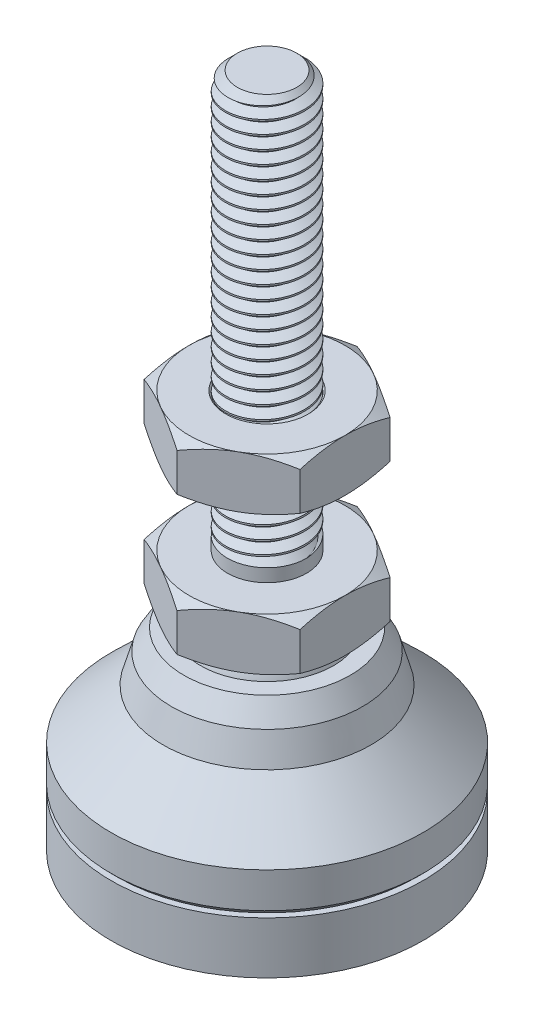
SolidWorks part; units mm, degrees
ref_plane "Front Plane" through (0, 0, 0) normal (0, 0, 1) x (1, 0, 0)
ref_plane "Top Plane" through (0, 0, 0) normal (0, 1, 0) x (1, 0, 0)
ref_plane "Right Plane" through (0, 0, 0) normal (1, 0, 0) x (0, 0, -1)
sketch "Sketch1" plane through (0, 0, 0) normal (0, 0, 1) x (1, 0, 0)
  line L0 (0, 0) -> (0, 41.275) construction
  line L1 (-9.525, 0) -> (9.525, 0) construction
  line L2 (-2.413, 41.275) -> (2.413, 41.275) construction
  line L3 (-4.7625, 12.7) -> (4.7625, 12.7) construction
  point P7 (0, 15.875)
  point P10 (0, 12.7)
  point P11 (-4.7625, 15.875)
  point P12 (0, 3.175)
  dimension "D1" = 3.175
sketch "Sketch2" plane through (0, 0, 0) normal (0, 0, 1) x (1, 0, 0)
  line L0 (0, 3.175) -> (0, 6.2865)
  line L1 (-4.2545, 12.7) -> (-4.7625, 12.7) construction
  line L2 (-5.842, 10.541) -> (-5.08, 11.811)
  line L3 (-5.08, 11.811) -> (-4.0605, 11.811)
  line L4 (-5.842, 10.541) -> (-6.35, 8.763)
  line L5 (-6.35, 8.763) -> (-9.525, 5.715)
  line L6 (-9.525, 5.715) -> (-9.525, 3.556)
  line L7 (-9.144, 3.175) -> (0, 3.175)
  line L8 (-5.842, 10.541) -> (0, 10.541) construction
  line L9 (-4.2545, 10.541) -> (-4.2545, 12.7) construction
  line L10 (-9.525, 3.556) -> (-9.144, 3.175)
  line L11 (-9.144, 3.175) -> (-9.525, 3.175) construction
  line L12 (-9.525, 3.175) -> (-9.525, 3.556) construction
  line L13 (0, 12.7) -> (0, 41.275) construction
  line L14 (-2.413, 41.275) -> (2.413, 41.275) construction
  line L15 (-4.7625, 12.7) -> (4.7625, 12.7) construction
  circle A0 centre (0, 10.541) radius 4.2545 construction
  arc A2 (-4.0605, 11.811) -> (0, 6.2865) centre (0, 10.541) ccw
  dimension "D1" = 12.7
  dimension "D2" = 11.684
  dimension "D3" = 10.16
  dimension "D4" = 0.508
  dimension "H3" = 1.778
  dimension "C1" = 0.381
  dimension "H4" = 1.27
  dimension "H2" = 3.048
  dimension "H1" = 2.54
revolve "Revolve1" add sketch "Sketch2" angle 360 about L0
sketch "Sketch12" plane through (0, 0, 0) normal (0, 0, 1) x (1, 0, 0)
  line L0 (0, 12.7) -> (-3.666, 12.7)
  line L1 (0, 12.7) -> (0, 6.2865)
  arc A0 (-3.666, 12.7) -> (0, 6.2865) centre (0, 10.541) ccw
  circle A1 centre (0, 10.541) radius 4.2545 construction
revolve "Revolve2" add sketch "Sketch12" angle 360 about L1
sketch "Sketch4" plane through (0, 12.7, 0) normal (0, 1, 0) x (1, 0, 0)
  line L1 (0, 5.4993) -> (-4.7625, 2.7496)
  line L2 (-4.7625, 2.7496) -> (-4.7625, -2.7496)
  line L3 (-4.7625, -2.7496) -> (0, -5.4993)
  line L4 (0, -5.4993) -> (4.7625, -2.7496)
  line L5 (4.7625, -2.7496) -> (4.7625, 2.7496)
  line L6 (4.7625, 2.7496) -> (0, 5.4993)
  circle A0 centre (0, 0) radius 4.7625 construction
extrude "Boss-Extrude1" add sketch "Sketch4" along normal up to vertex (3.175 mm away) up to point (0, 15.875, 0)
sketch "Sketch5" plane through (0, 0, 0) normal (1, 0, 0) x (0, 0, -1)
  line L0 (-6.236, 15.875) -> (-6.236, 12.7)
  line L1 (-6.236, 12.7) -> (-4.7625, 12.7)
  line L2 (-4.7625, 12.7) -> (-5.4993, 13.1254)
  line L3 (-5.4993, 13.1254) -> (-5.4993, 15.4496)
  line L4 (-5.4993, 15.4496) -> (-4.7625, 15.875)
  line L5 (-4.7625, 15.875) -> (-6.236, 15.875)
  line L9 (-5.4993, 15.875) -> (-5.4993, 12.7) construction
  dimension "D1" = 30
revolve "Cut-Revolve2" cut sketch "Sketch5" angle 360 about L0
sketch "Sketch6" plane through (0, 15.875, 0) normal (0, 1, 0) x (1, 0, 0)
  circle A0 centre (0, 0) radius 2.413
extrude "Boss-Extrude2" add sketch "Sketch6" along normal up to vertex (25.4 mm away) separate body up to point (0, 41.275, 0)
sketch "Sketch7" plane through (0, 41.275, 0) normal (0, 1, 0) x (1, 0, 0)
  circle A1 centre (0, 0) radius 2.413
  circle A2 centre (0, 0) radius 2.413
  point P0 (2.413, 0)
  dimension "D1" = 0
curve "Helix/Spiral1" pitch 0.7937 height 26.1937 turns 33 parameters "Pitch"=0.7937
sketch "Sketch8" plane through (0, 0, 0) normal (0, 0, 1) x (1, 0, 0)
  line L0 (2.4989, 42.0191) -> (2.4989, 41.2254) construction
  line L1 (2.4989, 41.2254) -> (1.8115, 41.6223) construction
  line L2 (1.8115, 41.6223) -> (2.4989, 42.0191) construction
  line L3 (1.8974, 41.6719) -> (1.8974, 41.5727) construction
  line L4 (2.413, 41.9695) -> (2.413, 41.275) construction
  line L5 (1.8115, 41.6223) -> (1.8974, 41.6223) construction
  line L6 (2.413, 41.6223) -> (2.4989, 41.6223) construction
  line L7 (2.456, 41.9943) -> (1.8974, 41.6719)
  line L8 (1.8974, 41.6719) -> (1.8974, 41.5727)
  line L9 (1.8974, 41.5727) -> (2.456, 41.2502)
  line L10 (2.456, 41.2502) -> (2.456, 41.9943)
  line L11 (2.4989, 41.2254) -> (2.413, 41.2254) construction
  line L12 (2.413, 41.2254) -> (2.413, 28.5254) construction
  line L20 (2.413, 15.875) -> (2.413, 41.275) construction
  point P11 (2.456, 41.6223)
  dimension "D1" = 0.7937
  dimension "D2" = 0.0992
  dimension "D3" = 12.7
sketch "Sketch9" plane through (0, 41.275, 0) normal (0, 1, 0) x (1, 0, 0)
  circle A0 centre (0, 0) radius 1.8115
sweep "Cut-Sweep1" cut profiles "Sketch8" path "Helix/Spiral1" align with end faces yes
extrude "Cut-Extrude1" cut sketch "Sketch9" against normal up to vertex (25.4 mm away) draft 45 flip side to cut up to point (0, 15.875, 0)
combine bodies "Combine1" operation type add bodies to combine 107 104
ref_plane "Plane1" through (0, 24.3417, 0) normal (0, 1, 0) x (-1, 0, 0)
sketch "Sketch10" plane through (0, 24.3417, 0) normal (0, 1, 0) x (-1, 0, 0)
  line L1 (0, 5.4993) -> (-4.7625, 2.7496)
  line L2 (-4.7625, 2.7496) -> (-4.7625, -2.7496)
  line L3 (-4.7625, -2.7496) -> (0, -5.4993)
  line L4 (0, -5.4993) -> (4.7625, -2.7496)
  line L5 (4.7625, -2.7496) -> (4.7625, 2.7496)
  line L6 (4.7625, 2.7496) -> (0, 5.4993)
  circle A0 centre (0, 0) radius 4.7625 construction
  circle A1 centre (0, 0) radius 2.413
  dimension "Nut Width" = 9.525
extrude "Boss-Extrude3" add sketch "Sketch10" against normal blind 3.175 separate body
sketch "Sketch11" plane through (0, 0, 0) normal (1, 0, 0) x (0, 0, -1)
  line L0 (-6.236, 21.1667) -> (-6.236, 24.3417)
  line L1 (-6.236, 24.3417) -> (-4.7625, 24.3417)
  line L2 (-4.7625, 24.3417) -> (-5.4993, 23.9163)
  line L3 (-5.4993, 23.9163) -> (-5.4993, 21.592)
  line L4 (-5.4993, 21.592) -> (-4.7625, 21.1667)
  line L5 (-4.7625, 21.1667) -> (-6.236, 21.1667)
  line L6 (-5.4993, 21.1667) -> (-5.4993, 24.3417) construction
  line L11 (0, 21.1667) -> (0, 24.3417)
  line L12 (0, 24.3417) -> (2.5122, 24.3417)
  line L13 (2.5122, 24.3417) -> (2.413, 24.2424)
  line L14 (2.413, 24.2424) -> (2.413, 21.2659)
  line L15 (2.413, 21.2659) -> (2.5122, 21.1667)
  line L16 (2.5122, 21.1667) -> (0, 21.1667)
  line L17 (2.413, 21.1667) -> (2.413, 24.3417) construction
  line L19 (0, 0) -> (0, 41.275) construction
  dimension "D2" = 45
  dimension "D3" = 0.0992
  dimension "D1" = 60
revolve "Cut-Revolve3" cut sketch "Sketch11" angle 360 about L0
sketch "Sketch13" plane through (0, 0, 0) normal (0, 0, 1) x (1, 0, 0)
  line L0 (0, 0) -> (0, 41.275) construction
  line L1 (0, 19.0817) -> (2.413, 16.6687)
  line L2 (0, 19.0817) -> (0, 15.875)
  line L3 (0, 15.875) -> (2.413, 15.875)
  line L4 (2.413, 16.6687) -> (2.413, 15.875)
  dimension "D1" = 45
  dimension "D2" = 0.7937
revolve "Revolve3" add sketch "Sketch13" angle 360 about L2
sketch "SketchX" plane through (0, 0, 0) normal (0, 0, 1) x (1, 0, 0)
  line L0 (0, 10.541) -> (-4.0116, 41.0121)
  line L1 (0, 10.541) -> (4.0116, 41.0121)
  line L2 (0, 0) -> (0, 41.275) construction
  line L3 (0, 10.541) -> (0, 41.275)
  arc A0 (-4.0116, 41.0121) -> (4.0116, 41.0121) centre (0, 10.541) cw construction
  dimension "D1" = 7.5
sketch "Sketch14" plane through (0, 0, 0) normal (0, 0, 1) x (1, 0, 0)
  line L1 (0, 0) -> (9.525, 0)
  line L2 (0, 0) -> (0, 3.175)
  line L3 (0, 3.175) -> (9.525, 3.175)
  line L4 (9.525, 0) -> (9.525, 3.175)
  point P5 (9.525, 1.5875)
revolve "Revolve4" add sketch "Sketch14" angle 360 about L2
equation "\"D3@Helix/Spiral1\" = \"Pitch@Helix/Spiral1\" + \"Thread Lg.@Sketch1\""
equation "\"D1@Sketch8\" = \"Pitch@Helix/Spiral1\" "
equation "\"D2@Sketch8\" = \"D1@Sketch8\" / 8"
equation "\"D1@Plane1\" = \"Thread Lg.@Sketch1\" / 1.5"
equation "\"D3@Sketch11\" = \"Pitch@Helix/Spiral1\" / 8"
equation "\"D2@Sketch13\" = \"Pitch@Helix/Spiral1\""
equation "\"D3@Sketch8\" = \"Thread Lg.@Sketch1\" / 2"
